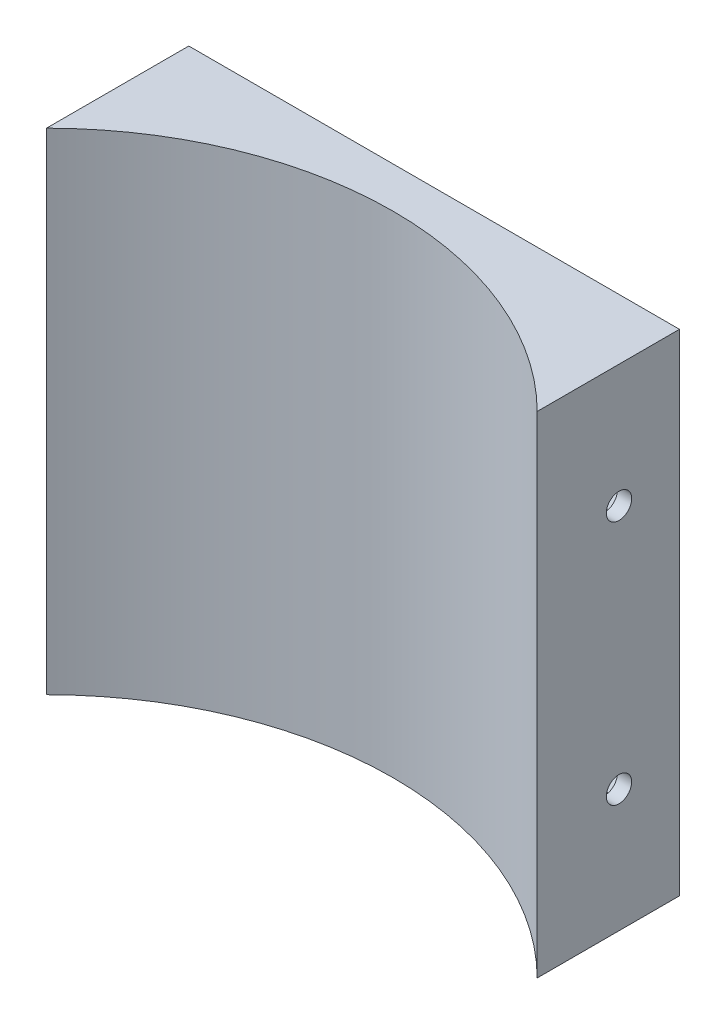
SolidWorks part; units mm, degrees
material "PVC 0.007 Plasticizado"
ref_plane "Plano frontal" through (0, 0, 0) normal (0, 0, 1) x (1, 0, 0)
ref_plane "Plano superior" through (0, 0, 0) normal (0, 1, 0) x (1, 0, 0)
ref_plane "Plano direito" through (0, 0, 0) normal (1, 0, 0) x (0, 0, -1)
sketch "Esboço2" plane through (0, 0, 0) normal (0, 1, 0) x (1, 0, 0)
  line L0 (-60, 0) -> (60, 0)
  line L1 (-60, -34.792) -> (-60, 0)
  line L2 (60, 0) -> (60, -34.792)
  arc A0 (-60, -34.792) -> (60, -34.792) centre (0, -95) cw
  point P4 (0, 0)
  point P8 (0, -10)
  dimension "D2" = 85
  dimension "D1" = 120
  dimension "D3" = 10
extrude "Ressalto-extrusão1" add sketch "Esboço2" along normal mid plane 120
shell "Casca1" thickness 3.5 removed face at (0, 0, 0)
ref_plane "Plano1" through (0, 0, 0) normal (0, 0, -1) x (-1, 0, 0)
sketch "Esboço7" plane through (0, 0, 0) normal (0, 0, -1) x (-1, 0, 0)
  line L5 (-56.5, -56.5) -> (56.5, -56.5)
  line L6 (-56.5, -56.5) -> (-56.5, 56.5)
  line L11 (-56.5, 56.5) -> (56.5, 56.5)
  line L12 (56.5, -56.5) -> (56.5, 56.5)
  line L13 (-56.5, -56.5) -> (56.5, 56.5) construction
  line L14 (-56.5, 56.5) -> (56.5, -56.5) construction
  line L15 (-52, -52) -> (52, -52)
  line L16 (-52, -52) -> (-52, 52)
  line L17 (-52, 52) -> (52, 52)
  line L18 (52, -52) -> (52, 52)
  line L19 (-52, -52) -> (52, 52) construction
  line L20 (-52, 52) -> (52, -52) construction
  point P0 (0, 0)
  point P5 (0, 0)
  dimension "D1" = 113
  dimension "D2" = 104
  dimension "D3" = 104
extrude "Ressalto-extrusão3" add sketch "Esboço7" along normal mid plane 6 separate body
chamfer "Chanfro1" distance 1 angle 45 4 edges at (56.5, 0, -3) (0, -56.5, -3) (-56.5, 0, -3) (0, 56.5, -3)
sketch "Esboço3" plane through (0, 0, 0) normal (0, 0, -1) x (-1, 0, 0)
  line L0 (-46.5, 51.5) -> (-46.5, 56.5)
  line L1 (-56.5, 56.5) -> (56.5, 56.5) construction
  line L2 (-56.5, 56.5) -> (-56.5, -56.5) construction
  line L3 (-56.5, 56.5) -> (56.5, 56.5) construction
  line L4 (-46.5, 56.5) -> (-56.5, 56.5)
  line L5 (-51.5, 46.5) -> (-56.5, 46.5)
  line L6 (-56.5, 56.5) -> (-56.5, -56.5) construction
  line L7 (-56.5, 46.5) -> (-56.5, 56.5)
  line L8 (0, 55) -> (0, -55) construction
  line L9 (56.5, 46.5) -> (56.5, 56.5)
  line L10 (51.5, 46.5) -> (56.5, 46.5)
  line L11 (46.5, 56.5) -> (56.5, 56.5)
  line L12 (46.5, 51.5) -> (46.5, 56.5)
  line L13 (55, 0) -> (-55, 0) construction
  line L14 (46.5, -51.5) -> (46.5, -56.5)
  line L15 (46.5, -56.5) -> (56.5, -56.5)
  line L16 (51.5, -46.5) -> (56.5, -46.5)
  line L17 (56.5, -46.5) -> (56.5, -56.5)
  line L18 (-56.5, -46.5) -> (-56.5, -56.5)
  line L19 (-51.5, -46.5) -> (-56.5, -46.5)
  line L20 (-46.5, -56.5) -> (-56.5, -56.5)
  line L21 (-46.5, -51.5) -> (-46.5, -56.5)
  line L22 (-51.5, 5) -> (-56.5, 5)
  line L23 (-56.5, 5) -> (-56.5, -5)
  line L24 (-56.5, -5) -> (-51.5, -5)
  line L25 (56.5, -5) -> (51.5, -5)
  line L26 (56.5, 5) -> (56.5, -5)
  line L27 (51.5, 5) -> (56.5, 5)
  line L28 (-5, 51.5) -> (-5, 56.5)
  line L29 (5, 51.5) -> (5, 56.5)
  line L30 (5, 56.5) -> (-5, 56.5)
  line L31 (5, -56.5) -> (-5, -56.5)
  line L32 (5, -51.5) -> (5, -56.5)
  line L33 (-5, -51.5) -> (-5, -56.5)
  arc A0 (-51.5, 46.5) -> (-46.5, 51.5) centre (-51.5, 51.5) ccw
  arc A1 (51.5, 46.5) -> (46.5, 51.5) centre (51.5, 51.5) cw
  arc A2 (51.5, -46.5) -> (46.5, -51.5) centre (51.5, -51.5) ccw
  arc A3 (-51.5, -46.5) -> (-46.5, -51.5) centre (-51.5, -51.5) cw
  arc A4 (-51.5, -5) -> (-51.5, 5) centre (-51.5, 0) ccw
  arc A5 (51.5, -5) -> (51.5, 5) centre (51.5, 0) cw
  arc A6 (-5, 51.5) -> (5, 51.5) centre (0, 51.5) ccw
  arc A7 (-5, -51.5) -> (5, -51.5) centre (0, -51.5) cw
  dimension "D1" = 10
  dimension "D2" = 10
  dimension "D3" = 10
extrude "Ressalto-extrusão2" add sketch "Esboço3" against normal through all
sketch "Esboço8" plane through (0, 0, 0) normal (0, 0, 1) x (1, 0, 0)
  line L0 (-46.5, 51.5) -> (-46.5, 56.5)
  line L4 (-46.5, 56.5) -> (-56.5, 56.5)
  line L5 (-51.5, 46.5) -> (-56.5, 46.5)
  line L7 (-56.5, 46.5) -> (-56.5, 56.5)
  line L9 (56.5, 46.5) -> (56.5, 56.5)
  line L10 (51.5, 46.5) -> (56.5, 46.5)
  line L11 (46.5, 56.5) -> (56.5, 56.5)
  line L12 (46.5, 51.5) -> (46.5, 56.5)
  line L14 (46.5, -51.5) -> (46.5, -56.5)
  line L15 (46.5, -56.5) -> (56.5, -56.5)
  line L16 (51.5, -46.5) -> (56.5, -46.5)
  line L17 (56.5, -46.5) -> (56.5, -56.5)
  line L18 (-56.5, -46.5) -> (-56.5, -56.5)
  line L19 (-51.5, -46.5) -> (-56.5, -46.5)
  line L20 (-46.5, -56.5) -> (-56.5, -56.5)
  line L21 (-46.5, -51.5) -> (-46.5, -56.5)
  line L22 (-51.5, 5) -> (-56.5, 5)
  line L23 (-56.5, 5) -> (-56.5, -5)
  line L24 (-56.5, -5) -> (-51.5, -5)
  line L25 (56.5, -5) -> (51.5, -5)
  line L26 (56.5, 5) -> (56.5, -5)
  line L27 (51.5, 5) -> (56.5, 5)
  line L28 (-5, 51.5) -> (-5, 56.5)
  line L29 (5, 51.5) -> (5, 56.5)
  line L30 (5, 56.5) -> (-5, 56.5)
  line L31 (5, -56.5) -> (-5, -56.5)
  line L32 (5, -51.5) -> (5, -56.5)
  line L33 (-5, -51.5) -> (-5, -56.5)
  arc A0 (-51.5, 46.5) -> (-46.5, 51.5) centre (-51.5, 51.5) ccw
  arc A1 (51.5, 46.5) -> (46.5, 51.5) centre (51.5, 51.5) cw
  arc A2 (51.5, -46.5) -> (46.5, -51.5) centre (51.5, -51.5) ccw
  arc A3 (-51.5, -46.5) -> (-46.5, -51.5) centre (-51.5, -51.5) cw
  arc A4 (-51.5, -5) -> (-51.5, 5) centre (-51.5, 0) ccw
  arc A5 (51.5, -5) -> (51.5, 5) centre (51.5, 0) cw
  arc A6 (-5, 51.5) -> (5, 51.5) centre (0, 51.5) ccw
  arc A7 (-5, -51.5) -> (5, -51.5) centre (0, -51.5) cw
  dimension "D1" = 10
  dimension "D2" = 10
  dimension "D3" = 10
extrude "Corte-extrusão2" cut sketch "Esboço8" against normal blind 3
sketch "Esboço9" plane through (-60, 0, 0) normal (-1, 0, 0) x (0, 0, 1)
  line L0 (34.792, 60) -> (34.792, -60) construction
  line L1 (0, 60) -> (34.792, 60) construction
  circle A0 centre (14.792, 30) radius 3.1
  circle A1 centre (14.792, -30) radius 3.1
  dimension "D1" = 6.2
  dimension "D2" = 20
  dimension "D5" = 6.2
  dimension "D6" = 20
  dimension "D3" = 30
  dimension "D4" = 60
extrude "Corte-extrusão3" cut sketch "Esboço9" against normal blind 5
mirror "Espelhar1" about plane through (0, 0, 0) normal (1, 0, 0) of "Corte-extrusão3"
sketch "Esboço10" plane through (-56.5, 0, 0) normal (1, 0, 0) x (0, 0, -1)
  line L1 (-8.9897, 30) -> (-11.8908, 35.025)
  line L2 (-11.8908, 35.025) -> (-17.6932, 35.025)
  line L3 (-17.6932, 35.025) -> (-20.5944, 30)
  line L4 (-20.5944, 30) -> (-17.6932, 24.975)
  line L5 (-17.6932, 24.975) -> (-11.8908, 24.975)
  line L6 (-11.8908, 24.975) -> (-8.9897, 30)
  circle A0 centre (-14.792, 30) radius 5.025 construction
  circle A1 centre (-14.792, 30) radius 7.5
  dimension "D2" = 15
  dimension "D1" = 10.05
extrude "Ressalto-extrusão4" add sketch "Esboço10" along normal blind 4.5
mirror "Espelhar2" about plane through (0, 0, 0) normal (0, 1, 0) of "Ressalto-extrusão4"
mirror "Espelhar3" about plane through (0, 0, 0) normal (1, 0, 0) of "Espelhar2"
sketch "Esboço11" plane through (0, 0, 0) normal (0, 1, 0) x (1, 0, 0)
  line L0 (-60, -34.792) -> (60, -34.792)
  arc A0 (-60, -34.792) -> (60, -34.792) centre (0, -95) cw
extrude "Corte-extrusão4" cut sketch "Esboço11" against normal through all both and the other way through all
